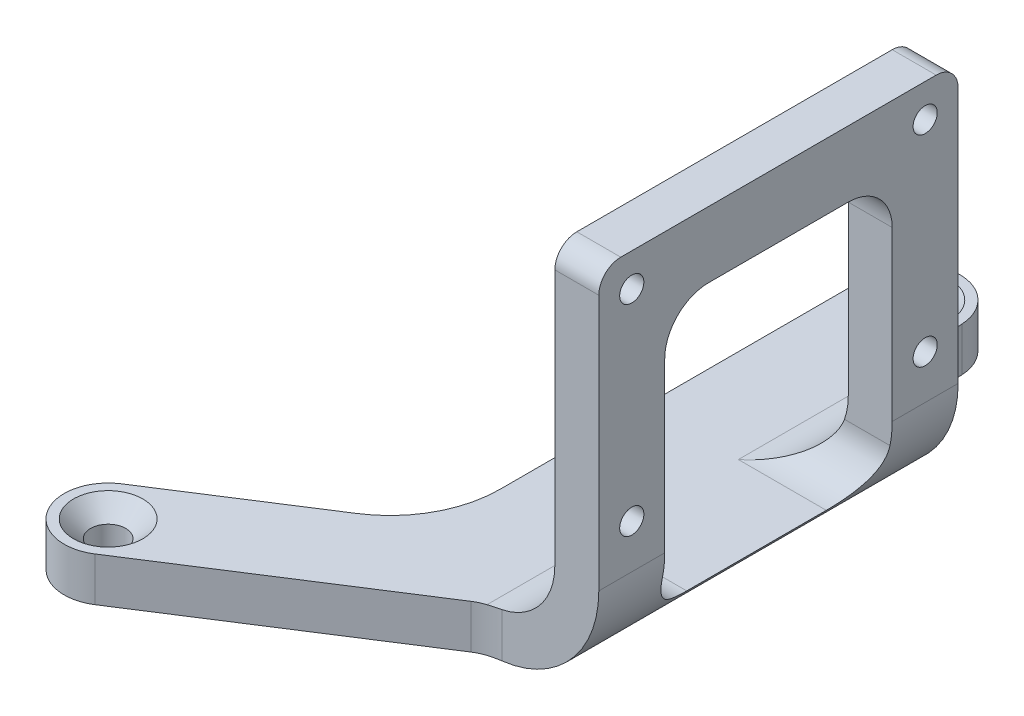
SolidWorks part; units mm, degrees
material "ABS"
ref_plane "Plan de face" through (0, 0, 0) normal (0, 0, 1) x (1, 0, 0)
ref_plane "Plan de dessus" through (0, 0, 0) normal (0, 1, 0) x (1, 0, 0)
ref_plane "Plan de droite" through (0, 0, 0) normal (1, 0, 0) x (0, 0, -1)
sketch "Esquisse1" plane through (0, 0, 0) normal (0, 0, 1) x (1, 0, 0)
  line L0 (0, 35.3) -> (0, 10)
  line L1 (-10, 0) -> (-38, 0)
  line L2 (-4, 35.3) -> (-4, 10)
  line L3 (-10, 4) -> (-38, 4)
  line L4 (0, 35.3) -> (-4, 35.3)
  line L5 (-38, 0) -> (-38, 4)
  arc A0 (0, 10) -> (-10, 0) centre (-10, 10) cw
  arc A1 (-4, 10) -> (-10, 4) centre (-10, 10) cw
  point P6 (0, 0)
  dimension "D3" = 10
  dimension "D1" = 38
  dimension "D2" = 35.3
  dimension "D4" = 4
extrude "Boss.-Extru.1" add sketch "Esquisse1" along normal blind 62
hole_wizard "Fraisage pour vis à tête fraisée M31" positions "Esquisse3" profile "Esquisse4" countersink size "M3" standard "ISO" end condition through all
sketch "Esquisse3" plane through (0, 4, 0) normal (0, 1, 0) x (1, 0, 0)
  line L0 (-38, -62) -> (-38, 0) construction
  line L1 (-10, -62) -> (-38, -62) construction
  point P0 (-34, -58)
  point P2 (-14.5, -4)
  dimension "D1" = 4
  dimension "D2" = 4
  dimension "D3" = 54
  dimension "D4" = 19.5
sketch "Esquisse4" plane through (-34, 4, 58) normal (1, 0, 0) x (0, 0, 1)
  line L0 (0, 0) -> (0, 4)
  line L1 (0, 4) -> (1.6, 4)
  line L2 (1.6, 4) -> (1.6, 1.55)
  line L3 (1.6, 1.55) -> (3.15, 0)
  line L5 (3.15, 0) -> (0, 0)
  line L6 (-1.6, 1.55) -> (-3.15, 0) construction
  line L11 (0, -6.35) -> (0, 107.95) construction
  dimension "Diamètre du perçage jusqu'au prochain" = 3.2
  dimension "Profondeur du perçage jusqu'au prochain" = 4
  dimension "Diamètre du fraisage entrant" = 6.3
  dimension "Angle du fraisage entrant" = 90
hole_wizard "Fraisage pour vis à tête fraisée M21" positions "Esquisse8" profile "Esquisse9" countersink size "M2" standard "ISO" end condition through all
sketch "Esquisse8" plane through (-4, 0, 0) normal (-1, 0, 0) x (0, 0, 1)
  line L0 (62, 10) -> (0, 10) construction
  line L1 (17.65, 32.29) -> (44.35, 14) construction
  line L3 (0, 35.3) -> (62, 10) construction
  point P0 (17.65, 32.29)
  point P2 (44.35, 14)
  point P4 (44.35, 32.29)
  point P6 (17.65, 14)
  point P30 (31, 23.145)
  point P31 (31, 22.65)
  dimension "D1" = 26.7
  dimension "D2" = 18.29
  dimension "D3" = 4
sketch "Esquisse9" plane through (-4, 32.29, 17.65) normal (0, 1, 0) x (0, 0, 1)
  line L0 (0, 0) -> (0, 4)
  line L1 (0, 4) -> (1.1, 4)
  line L2 (1.1, 4) -> (1.1, 1.1)
  line L3 (1.1, 1.1) -> (2.2, 0)
  line L5 (2.2, 0) -> (0, 0)
  line L6 (-1.1, 1.1) -> (-2.2, 0) construction
  line L11 (0, -6.35) -> (0, 107.95) construction
  dimension "Diamètre du perçage jusqu'au prochain" = 2.2
  dimension "Profondeur du perçage jusqu'au prochain" = 4
  dimension "Diamètre du fraisage entrant" = 4.4
  dimension "Angle du fraisage entrant" = 90
sketch "Esquisse10" plane through (0, 0, 0) normal (1, 0, 0) x (0, 0, -1)
  line L0 (-0.85, 4) -> (-7.15, 4) construction
  line L1 (-62, 35.3) -> (-47.35, 35.3)
  line L2 (-62, 35.3) -> (-62, 4)
  line L3 (-62, 4) -> (-47.35, 4)
  line L4 (-47.35, 35.3) -> (-47.35, 4)
  line L5 (0, 35.3) -> (-14.65, 35.3)
  line L6 (0, 35.3) -> (0, 4)
  line L7 (0, 4) -> (-14.65, 4)
  line L8 (-14.65, 35.3) -> (-14.65, 4)
  line L10 (-37.35, 29.29) -> (-24.65, 29.29)
  line L11 (-41.35, 25.29) -> (-41.35, 8)
  line L12 (-37.35, 4) -> (-24.65, 4)
  line L13 (-20.65, 25.29) -> (-20.65, 8)
  circle A0 centre (-17.65, 32.29) radius 1.1 construction
  circle A1 centre (-44.35, 32.29) radius 1.1 construction
  circle A2 centre (-44.35, 14) radius 1.1 construction
  arc A4 (-41.35, 8) -> (-37.35, 4) centre (-37.35, 8) ccw
  arc A5 (-24.65, 4) -> (-20.65, 8) centre (-24.65, 8) ccw
  arc A6 (-24.65, 29.29) -> (-20.65, 25.29) centre (-24.65, 25.29) cw
  arc A7 (-37.35, 29.29) -> (-41.35, 25.29) centre (-37.35, 25.29) ccw
  dimension "D1" = 3
  dimension "D3" = 3
  dimension "D7" = 4
  dimension "D2" = 3
  dimension "D5" = 3
  dimension "D6" = 3
extrude "Enlèv. mat.-Extru.1" cut sketch "Esquisse10" against normal blind 20
sketch "Esquisse11" plane through (0, 4, 0) normal (0, 1, 0) x (1, 0, 0)
  line L0 (-14.5, -4) -> (-14.5, -45.4851) construction
  line L1 (-14.5, -45.4851) -> (-34, -58) construction
  line L2 (-18.5, -4) -> (-18.5, -37.8349)
  line L3 (-23.0988, -46.2508) -> (-36.1605, -54.6337)
  line L4 (-10, -14.65) -> (-2, -14.65) construction
  line L6 (-10, -47.35) -> (-31.8395, -61.3663)
  line L7 (-2, -62) -> (-38, -62) construction
  line L8 (-18.5, -43.2994) -> (-36.1605, -54.6337) construction
  line L9 (-2, 0) -> (-14.5, 0)
  line L10 (-2, 0) -> (-2, -14.65)
  line L11 (-2, -14.65) -> (-10, -14.65)
  line L13 (-2, 0) -> (-38, 0) construction
  line L14 (-10, -14.65) -> (-10.5043, -3.814)
  line L15 (-18.5, -4) -> (-18.5, -43.2994) construction
  line L16 (-38, -58) -> (-38, 0)
  line L17 (-38, 0) -> (-14.5, 0)
  line L18 (-38, -58) -> (-38, -62)
  line L19 (-38, -62) -> (-34, -62)
  line L20 (-34, -62) -> (-2, -62)
  line L21 (-2, -62) -> (-2, -47.35)
  line L22 (-2, -47.35) -> (-10, -47.35)
  arc A0 (-36.1605, -54.6337) -> (-31.8395, -61.3663) centre (-34, -58) ccw
  arc A1 (-10.5043, -3.814) -> (-18.5, -4) centre (-14.5, -4) ccw
  arc A2 (-18.5, -37.8349) -> (-23.0988, -46.2508) centre (-28.5, -37.8349) cw
  point P12 (0, 0)
  line M5 (-2, -47.35) -> (-10, -47.35)
  line M7 (-10, -14.65) -> (-2, -14.65)
  line M8 (-2, -14.65) -> (-2, 0)
  line M9 (-2, 0) -> (-38, 0)
  line M10 (-38, 0) -> (-38, -62)
  line M11 (-38, -62) -> (-2, -62)
  line M12 (-2, -62) -> (-2, -47.35)
  dimension "D2" = 10
extrude "Enlèv. mat.-Extru.2" cut sketch "Esquisse11" against normal blind 20 contours A1 L14 M7 M8 M9 | A2 L2 A1 A0 L3 M9 M10 | A0 L6 M11 M12 M5 | A0 M10 M11 region at (-12.8341, 4, 56.1131) region at (-37.1065, 4, 61.1065) region at (-6.3034, 4, 7.0685) region at (-28.6721, 4, 24.7629)
fillet "Congé1" radius 2 2 edges at (-2, 35.3, 47.35) (-2, 35.3, 14.65)
fillet "Congé2" radius 4 2 edges at (-10, 2, 14.65) (-10, 2, 47.35)
